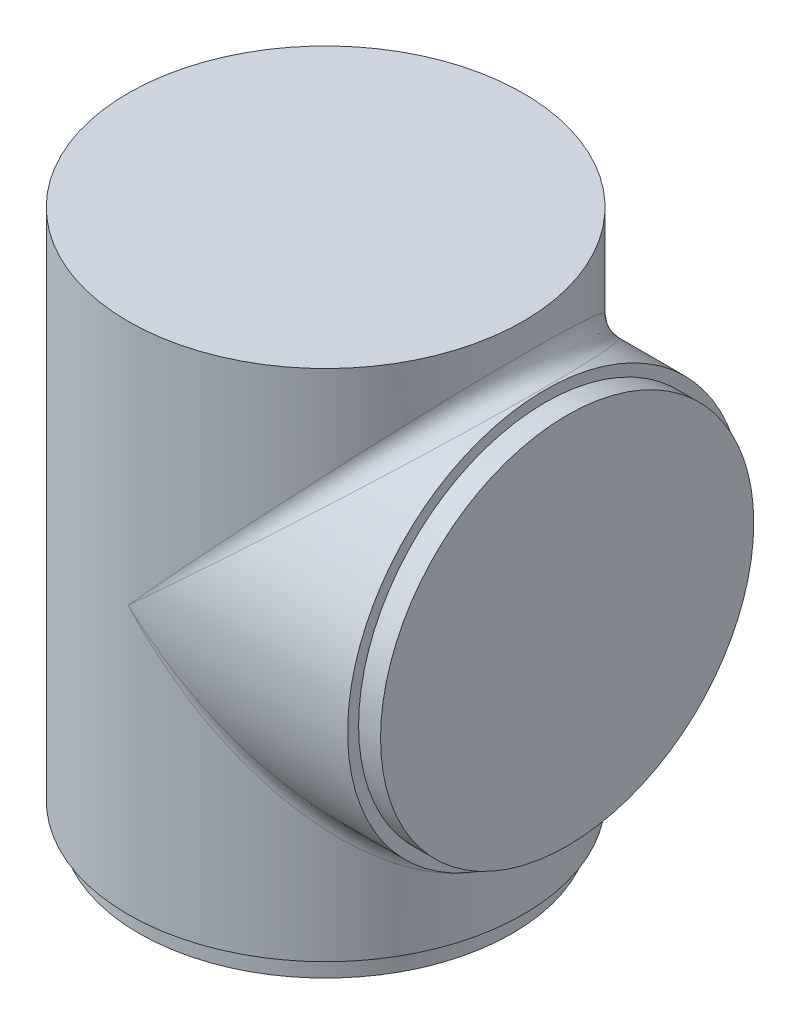
SolidWorks part; units mm, degrees
material "PP Copolymer"
ref_plane "Front Plane" through (0, 0, 0) normal (0, 0, 1) x (1, 0, 0)
ref_plane "Top Plane" through (0, 0, 0) normal (0, 1, 0) x (1, 0, 0)
ref_plane "Right Plane" through (0, 0, 0) normal (1, 0, 0) x (0, 0, -1)
sketch "Sketch1" plane through (0, 0, 0) normal (0, 1, 0) x (1, 0, 0)
  circle A0 centre (0, 0) radius 42.5
  dimension "D1" = 85
extrude "Boss-Extrude1" add sketch "Sketch1" along normal blind 5
sketch "Sketch2" plane through (0, 5, 0) normal (0, 1, 0) x (1, 0, 0)
  circle A0 centre (0, 0) radius 45
  dimension "D1" = 90
extrude "Boss-Extrude2" add sketch "Sketch2" along normal blind 117
sketch "Sketch3" plane through (0, 0, 0) normal (1, 0, 0) x (0, 0, -1)
  line L0 (0, 0) -> (0, 122) construction
  line L1 (45, 122) -> (-45, 122) construction
  line L2 (-45, 66) -> (45, 66) construction
  line L3 (-45, 122) -> (-45, 5) construction
  line L4 (45, 5) -> (45, 122) construction
  line L5 (-42.5, 0) -> (42.5, 0) construction
  circle A0 centre (0, 66) radius 45
  dimension "D2" = 90
  dimension "D1" = 66
extrude "Boss-Extrude3" add sketch "Sketch3" along normal blind 50 contours A0
fillet "Fillet4" radius 4.5 2 edges at (45, 111, 0) (45, 21, 0)
sketch "Sketch4" plane through (50, 0, 0) normal (1, 0, 0) x (0, 0, -1)
  circle A0 centre (0, 66) radius 42.5
  dimension "D1" = 85
extrude "Boss-Extrude4" add sketch "Sketch4" along normal blind 5
